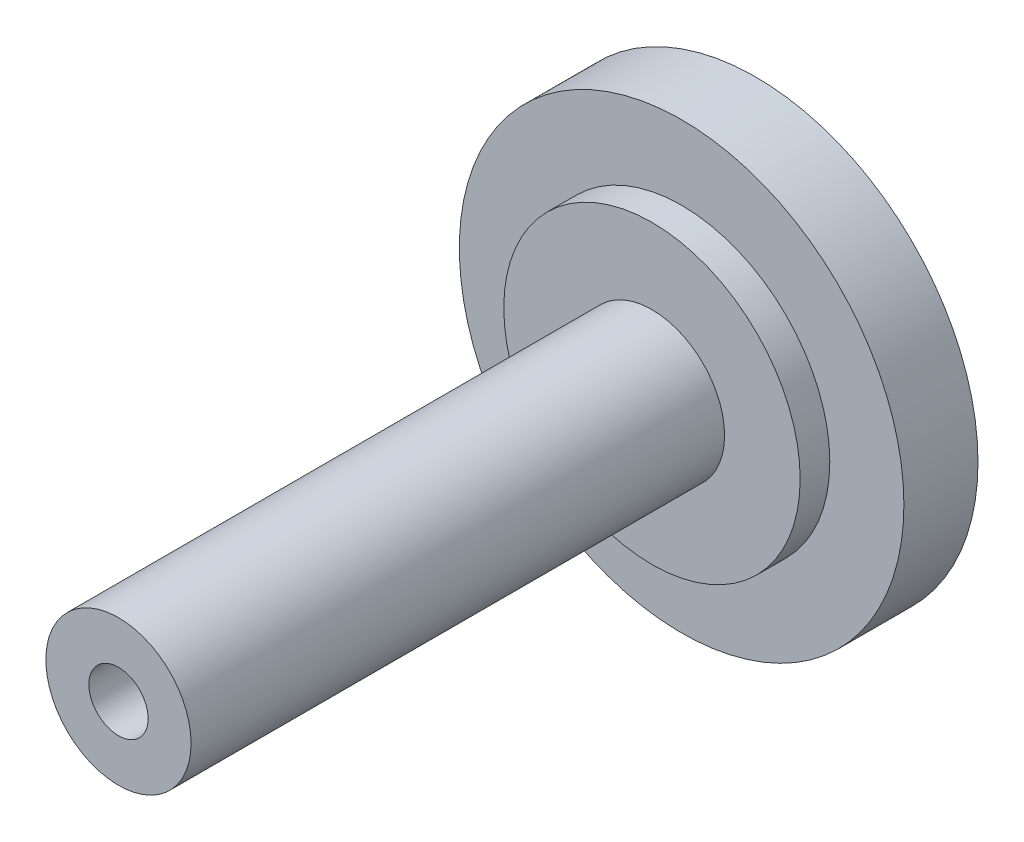
SolidWorks part; units mm, degrees
ref_plane "정면" through (0, 0, 0) normal (0, 0, 1) x (1, 0, 0)
ref_plane "윗면" through (0, 0, 0) normal (0, 1, 0) x (1, 0, 0)
ref_plane "우측면" through (0, 0, 0) normal (1, 0, 0) x (0, 0, -1)
sketch "스케치1" plane through (0, 0, 0) normal (0, 0, 1) x (1, 0, 0)
  circle A0 centre (0, 0) radius 7.5
  dimension "D1" = 15
extrude "보스-돌출1" add sketch "스케치1" along normal blind 2.5
sketch "스케치2" plane through (0, 0, 2.5) normal (0, 0, 1) x (1, 0, 0)
  circle A0 centre (0, 0) radius 5
  dimension "D1" = 10
extrude "보스-돌출2" add sketch "스케치2" along normal blind 1
sketch "스케치3" plane through (0, 0, 3.5) normal (0, 0, 1) x (1, 0, 0)
  circle A0 centre (0, 0) radius 2.45
  dimension "D1" = 4.9
extrude "보스-돌출3" add sketch "스케치3" along normal blind 18
sketch "스케치4" plane through (0, 0, 21.5) normal (0, 0, 1) x (1, 0, 0)
  circle A0 centre (0, 0) radius 1
  dimension "D1" = 2
extrude "컷-돌출1" cut sketch "스케치4" against normal blind 10
sketch "스케치5" plane through (0, 0, 0) normal (0, 1, 0) x (1, 0, 0)
  circle A0 centre (0, 0) radius 3
  dimension "D1" = 6
extrude "컷-돌출2" cut sketch "스케치5" against normal blind 3.1 and the other way blind 3.1
